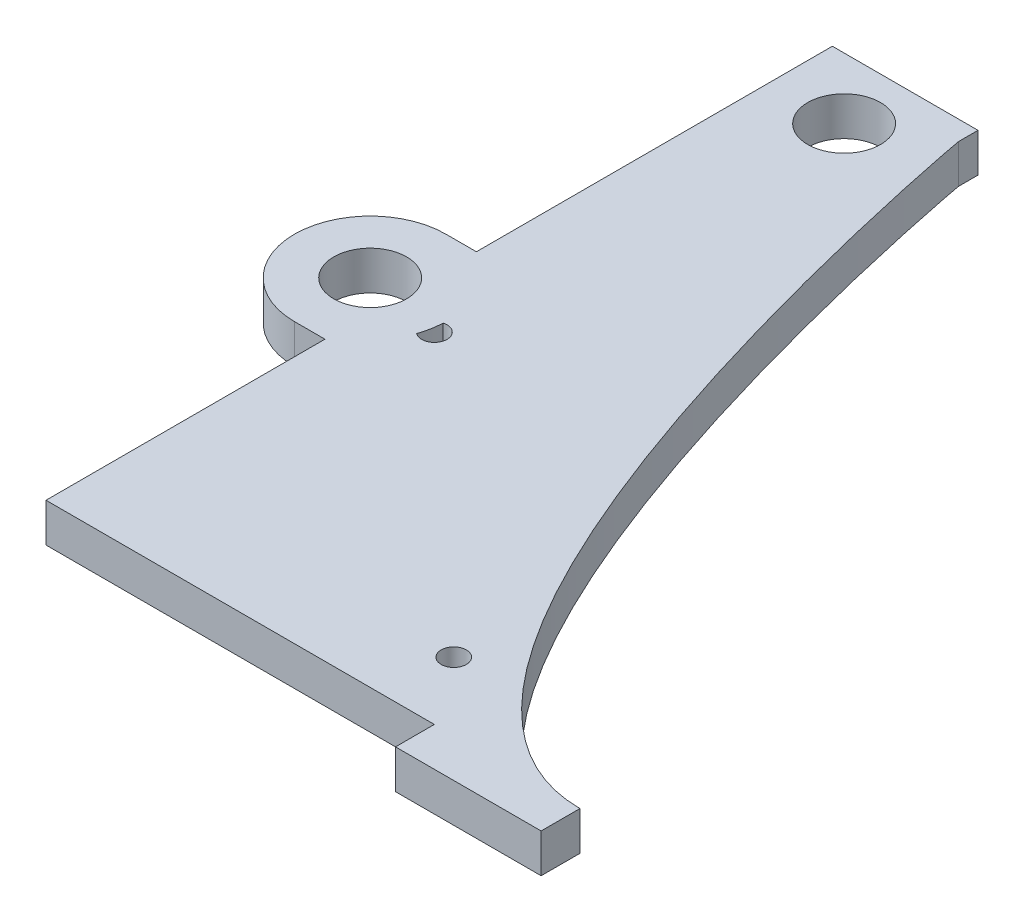
SolidWorks part; units mm, degrees
ref_plane "Front Plane" through (0, 0, 0) normal (0, 0, 1) x (1, 0, 0)
ref_plane "Top Plane" through (0, 0, 0) normal (0, 1, 0) x (1, 0, 0)
ref_plane "Right Plane" through (0, 0, 0) normal (1, 0, 0) x (0, 0, -1)
sketch "Sketch1" plane through (0, 0, 0) normal (0, 1, 0) x (1, 0, 0)
  line L0 (9.525, -53.975) -> (60.325, -53.975) construction
  line L1 (-9.525, -53.975) -> (9.525, -53.975) construction
  line L2 (-9.525, -53.975) -> (-9.525, 53.975) construction
  line L3 (-9.525, 53.975) -> (9.525, 53.975)
  line L4 (9.525, -53.975) -> (9.525, 53.975) construction
  line L5 (-9.525, -53.975) -> (9.525, 53.975) construction
  line L6 (-9.525, 53.975) -> (9.525, -53.975) construction
  line L7 (0, 53.975) -> (0, 45.9867) construction
  line L8 (-9.525, 50.7492) -> (9.525, 50.7492) construction
  line L9 (9.525, 51.435) -> (9.525, 53.975)
  line L10 (60.325, -53.975) -> (60.325, -48.895) construction
  line L11 (60.325, -48.895) -> (-9.525, -48.895) construction
  line L12 (60.325, -53.975) -> (60.325, -48.895) construction
  line L13 (60.325, -48.895) -> (-9.525, -48.895)
  line L14 (-9.525, -48.895) -> (-9.525, 53.975)
  line L15 (31.115, -19.685) -> (31.115, -48.895) construction
  circle A0 centre (0, 45.9867) radius 4.7625
  spline S0 degree 3 poles (9.525, 51.435) (9.525, 51.2145) (27.8191, -48.895) (60.325, -48.895) knots 0 0 0 0 1 1 1 1
  point P4 (0, 0)
  dimension "D5" = 9.525
  dimension "D1" = 107.95
  dimension "D2" = 19.05
  dimension "D3" = 50.8
  dimension "D4" = 2.54
  dimension "D6" = 104.7242
  dimension "D7" = 5.08
  dimension "D8" = 40.64
  dimension "D9" = 29.21
extrude "Boss-Extrude1" add sketch "Sketch1" along normal blind 5.08
sketch "Sketch4" plane through (0, 5.08, 0) normal (0, 1, 0) x (1, 0, 0)
  line L0 (-9.525, 53.975) -> (-9.525, -48.895) construction
  line L1 (60.325, -48.895) -> (41.275, -48.895)
  line L2 (60.325, -48.895) -> (60.325, -53.975)
  line L3 (60.325, -53.975) -> (41.275, -53.975)
  line L4 (41.275, -48.895) -> (41.275, -53.975)
  line L5 (60.325, -48.895) -> (41.275, -53.975) construction
  line L6 (60.325, -53.975) -> (41.275, -48.895) construction
  point P4 (50.8, -51.435)
  dimension "D1" = 50.8
  dimension "D2" = 5.08
extrude "Boss-Extrude2" add sketch "Sketch4" against normal up to surface (5.08 mm away) up to face at (17.145, 0, -2.286)
sketch "Sketch5" plane through (0, 0, 0) normal (0, -1, 0) x (1, 0, 0)
  circle A1 centre (34.925, 40.005) radius 1.651
  circle A3 centre (-3.175, 4.445) radius 1.6607
extrude "Cut-Extrude1" cut sketch "Sketch5" against normal through all both
sketch "Sketch6" plane through (0, 0, 0) normal (0, -1, 0) x (1, 0, 0)
  line L0 (-9.525, 2.4976) -> (-13.5128, 2.4976) construction
  line L1 (-9.525, -53.975) -> (-9.525, 48.895) construction
  line L2 (-13.5128, 12.4036) -> (-9.525, 12.4036)
  line L3 (-13.5128, -7.4084) -> (-9.525, -7.4084)
  line L4 (-9.525, 12.4036) -> (-9.525, 11.5655)
  line L5 (-9.525, -7.4084) -> (-9.525, -6.5703)
  line L7 (41.275, 53.975) -> (60.325, 53.975) construction
  circle A0 centre (-13.5128, 2.4976) radius 4.7625
  arc A1 (-9.525, -6.5703) -> (-9.525, 11.5655) centre (-13.5128, 2.4976) ccw
  arc A2 (-13.5128, 12.4036) -> (-13.5128, -7.4084) centre (-13.5128, 2.4976) ccw
  dimension "D1" = 9.525
  dimension "D3" = 9.906
  dimension "D2" = 3.9878
  dimension "D4" = 51.4774
extrude "Boss-Extrude3" add sketch "Sketch6" against normal blind 5.08
sketch "Sketch8" plane through (0, 5.08, 0) normal (0, 1, 0) x (1, 0, 0)
  circle A0 centre (-13.5128, -2.4976) radius 4.7625
extrude "Cut-Extrude2" cut sketch "Sketch8" against normal through all
